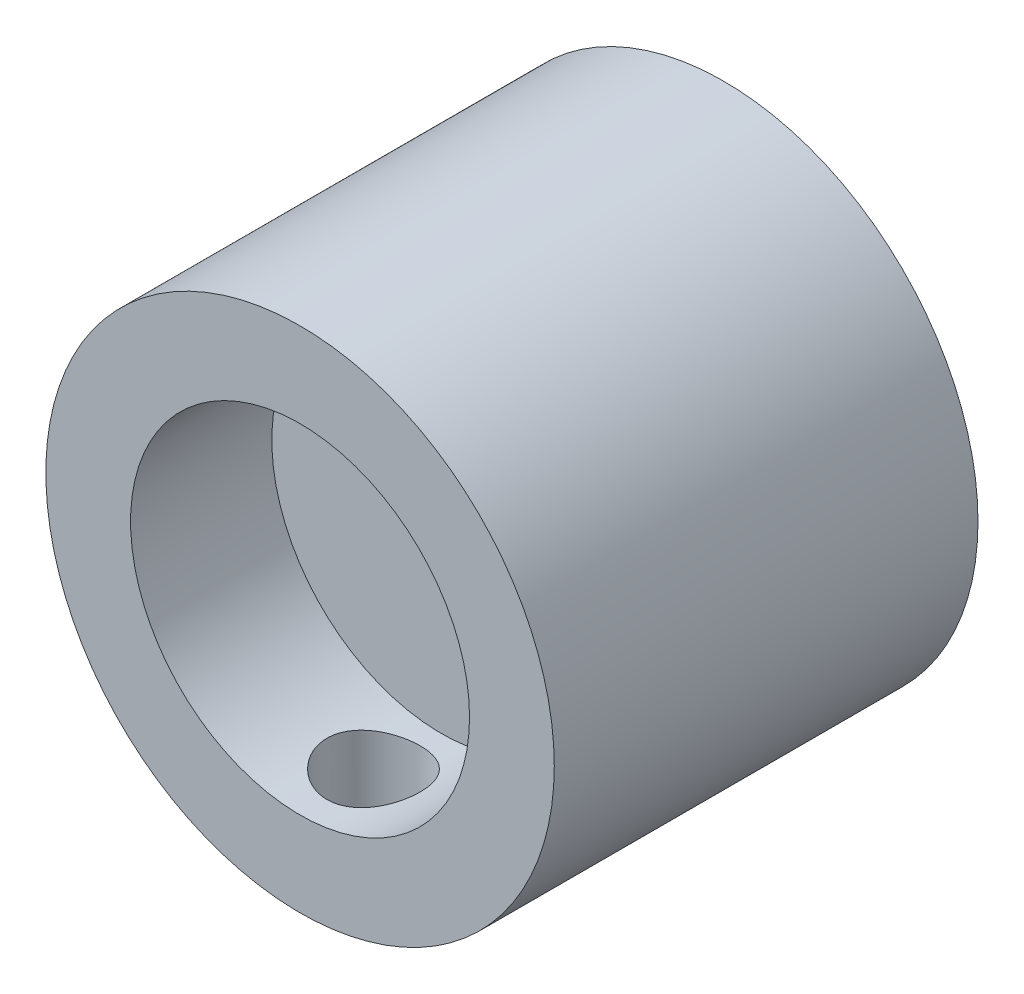
SolidWorks part; units mm, degrees
ref_plane "Front Plane" through (0, 0, 0) normal (0, 0, 1) x (1, 0, 0)
ref_plane "Top Plane" through (0, 0, 0) normal (0, 1, 0) x (1, 0, 0)
ref_plane "Right Plane" through (0, 0, 0) normal (1, 0, 0) x (0, 0, -1)
sketch "Sketch3" plane through (0, 0, 0) normal (0, 0, 1) x (1, 0, 0)
  circle A0 centre (0, 0) radius 4.5
  dimension "D1" = 9
extrude "Boss-Extrude3" add sketch "Sketch3" along normal blind 7.5
sketch "Sketch4" plane through (0, 0, 7.5) normal (0, 0, 1) x (1, 0, 0)
  circle A0 centre (0, 0) radius 3
  dimension "D1" = 6
extrude "Cut-Extrude1" cut sketch "Sketch4" against normal blind 2.5
sketch "Sketch5" plane through (0, 0, 0) normal (0, 0, -1) x (-1, 0, 0)
  circle A0 centre (0, 0) radius 2
  dimension "D1" = 4
extrude "Cut-Extrude2" cut sketch "Sketch5" against normal blind 1.9
sketch "Sketch7" plane through (0, 0, 0) normal (0, 1, 0) x (1, 0, 0)
  line L0 (0, 0) -> (0, -7.5) construction
  line L1 (4.5, 0) -> (-4.5, 0) construction
  line L2 (-4.5, -7.5) -> (4.5, -7.5) construction
  circle A0 centre (0, -6.2) radius 0.825
  dimension "D1" = 1.65
  dimension "D2" = 1.3
extrude "Cut-Extrude3" cut sketch "Sketch7" against normal up to next
